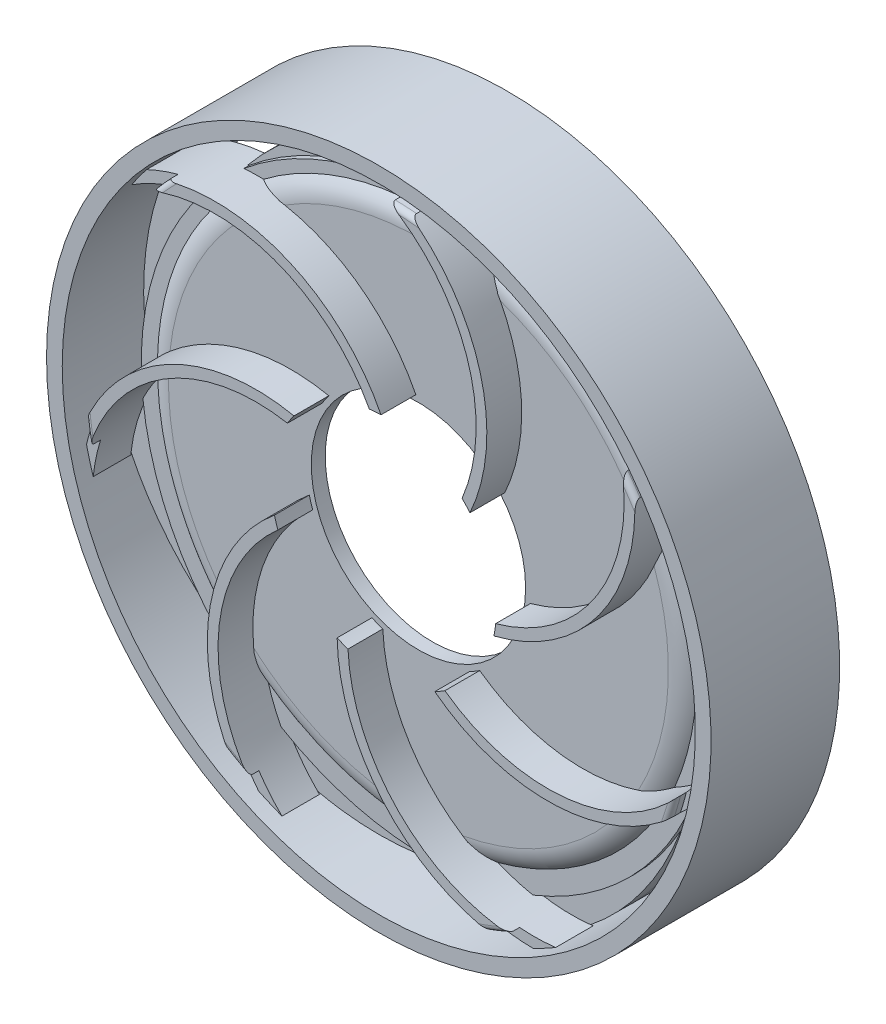
SolidWorks part; units mm, degrees
ref_plane "Ön Düzlem" through (0, 0, 0) normal (0, 0, 1) x (1, 0, 0)
ref_plane "Üst Düzlem" through (0, 0, 0) normal (0, 1, 0) x (1, 0, 0)
ref_plane "Sağ Düzlem" through (0, 0, 0) normal (1, 0, 0) x (0, 0, -1)
sketch "Sketch1" plane through (0, 0, 0) normal (0, 0, 1) x (1, 0, 0)
  circle A0 centre (0, 0) radius 51
extrude "Boss-Extrude1" add sketch "Sketch1" along normal blind 2.6
sketch "Sketch13" plane through (0, 0, 0) normal (0, 0, -1) x (-1, 0, 0)
  line L0 (0, 0) -> (0, 51) construction
  line L1 (0, 51) -> (0, 59.5)
  line L2 (0, 0) -> (39.8734, 31.798) construction
  line L3 (0, 0) -> (49.7213, -11.3486) construction
  line L4 (0, 0) -> (22.1281, -45.9494) construction
  line L5 (0, 0) -> (-22.1281, -45.9494) construction
  line L6 (0, 0) -> (-49.7213, -11.3486) construction
  line L7 (0, 0) -> (-39.8734, 31.798) construction
  line L8 (39.8734, 31.798) -> (46.519, 37.0976)
  line L9 (49.7213, -11.3486) -> (58.0082, -13.24)
  line L10 (22.1281, -45.9494) -> (25.8161, -53.6076)
  line L11 (-22.1281, -45.9494) -> (-25.8161, -53.6076)
  line L12 (-49.7213, -11.3486) -> (-58.0082, -13.24)
  line L13 (-39.8734, 31.798) -> (-46.519, 37.0976)
  circle A0 centre (0, 0) radius 51 construction
  circle A1 centre (0, 0) radius 51
  spline S0 degree 3 poles (39.8734, 31.798) (31.9324, 46.3417) (16.4942, 57.3969) (0, 59.5) knots 0 0 0 0 1 1 1 1
  spline S1 degree 3 poles (49.7213, -11.3486) (56.141, 3.9278) (55.1586, 22.8907) (46.519, 37.0976) knots 0 0 0 0 1 1 1 1
  spline S2 degree 3 poles (22.1281, -45.9494) (38.0742, -41.4438) (52.2875, -28.8526) (58.0082, -13.24) knots 0 0 0 0 1 1 1 1
  spline S3 degree 3 poles (-22.1281, -45.9494) (-8.6632, -55.6074) (10.0428, -58.8693) (25.8161, -53.6076) knots 0 0 0 0 1 1 1 1
  spline S4 degree 3 poles (-49.7213, -11.3486) (-48.8771, -27.8975) (-39.7643, -44.5562) (-25.8161, -53.6076) knots 0 0 0 0 1 1 1 1
  spline S5 degree 3 poles (-39.8734, 31.798) (-52.2855, 20.8198) (-59.6281, 3.3086) (-58.0082, -13.24) knots 0 0 0 0 1 1 1 1
  spline S6 degree 3 poles (0, 51) (-16.3219, 53.8594) (-34.5907, 48.682) (-46.519, 37.0976) knots 0 0 0 0 1 1 1 1
  circle M1 centre (0, 0) radius 51
extrude "Boss-Extrude12" add sketch "Sketch13" along normal blind 3.5 separate body contours S6 L13 M1 | S5 L12 M1 | S4 L11 M1 | S3 L10 M1 | S2 L9 M1 | S1 L8 M1 | S0 L1 M1 region at (-14.9152, 50.6485, 0) region at (30.2991, 43.24, 0) region at (-48.8981, 19.9176, 0) region at (52.6975, 3.2709, 0) region at (35.4137, -39.1612, 0) region at (-46.0596, -25.8116, 0) region at (-8.5374, -52.1042, 0)
sketch "Sketch17" plane through (0, 0, -3.5) normal (0, 0, -1) x (-1, 0, 0)
  circle A0 centre (0, 0) radius 51
  circle A1 centre (0, 0) radius 51.583
extrude "Boss-Extrude17" add sketch "Sketch17" against normal blind 3.55
sketch "Sketch18" plane through (0, 0, -3.5) normal (0, 0, -1) x (-1, 0, 0)
  line L0 (0, 59.5) -> (0, 57.9874)
  line L1 (0, 51.583) -> (0, 59.5) construction
  line L2 (38.1469, 34.7219) -> (37.6476, 34.4043)
  arc A0 (37.6476, 34.4043) -> (33.9454, 38.0618) centre (0, 0) ccw
  spline S0 degree 3 poles (-2791.739, 934.1905) (2717.5594, -1730.7665) (-2165.1588, 2407.9814) (1350.0187, -2586.5321) knots -6.738439 -6.738439 -6.738439 -6.738439 7.54991 7.54991 7.54991 7.54991 only from (38.1469, 34.7219) to (0, 59.5) construction
  spline S1 degree 3 poles (38.1469, 34.7219) (29.8227, 47.8074) (15.3698, 57.5402) (0, 59.5) knots 0.06817 0.06817 0.06817 0.06817 1 1 1 1
  spline S2 degree 1 poles (36.8813, 33.9168) (-0.1897, 58.012) knots 0 0 1 1 construction
  spline S3 degree 3 poles (36.8813, 33.9168) (35.867, 35.5112) (33.6642, 38.5799) (28.5725, 44.272) (21.107, 50.3681) (10.8625, 55.6485) (3.5383, 57.5367) (-0.1897, 58.012) knots 0.06817 0.06817 0.06817 0.06817 0.184649 0.301127 0.534085 0.767042 1 1 1 1 only from (33.9454, 38.0618) to (0, 57.9874)
  dimension "D1" = 1.5
extrude "Boss-Extrude18" add sketch "Sketch18" along normal blind 8
pattern_circular "CirPattern9" count 7 over 360 about axis through (0, 0, -3.5) along (0, 0, -1) of "Boss-Extrude18"
chamfer "Chamfer4" distance 8 distance2 6 7 edges at (49.1406, -14.6973, -11.5) (42.1295, 29.2561, -11.5) (3.394, 51.179, -11.5) (-37.8972, 34.5631, -11.5) (-50.6511, -8.0795, -11.5) (-25.2636, -44.6381, -11.5) (19.1479, -47.5833, -11.5) first distance on face at (49.0818, -14.6903, -6.7) first distance on face at (42.0874, 29.2145, -6.7) first distance on face at (3.4003, 51.1202, -6.7) first distance on face at (-37.8473, 34.5314, -6.7) first distance on face at (-50.5951, -8.0603, -6.7) first distance on face at (-25.2438, -44.5824, -6.7) first distance on face at (19.1167, -47.533, -6.7)
fillet "Fillet2" radius 5 1 edges at (51, 0, 2.6)
sketch "Sketch19" plane through (0, 0, -11.5) normal (0, 0, -1) x (-1, 0, 0)
  circle A0 centre (0, 0) radius 59.0701
  circle A1 centre (0, 0) radius 62
extrude "Boss-Extrude19" add sketch "Sketch19" along normal blind 2.5 and the other way blind 21.5
sketch "Sketch20" plane through (0, 0, 2.6) normal (0, 0, 1) x (1, 0, 0)
  line L0 (0, 0) -> (0, 51) construction
  circle A0 centre (0, 0) radius 51 construction
  circle A1 centre (0, 0) radius 20
extrude "Cut-Extrude2" cut sketch "Sketch20" against normal through all
sketch "Sketch21" plane through (0, 0, 2.6) normal (0, 0, 1) x (1, 0, 0)
  line L0 (0, 0) -> (0, 20) construction
  line L1 (0, 20) -> (-46.1002, 36.7637) construction
  line L2 (-40.3292, 32.1614) -> (-46.1829, 36.8296) construction
  line L3 (-23.0501, 28.3818) -> (-31.4228, 5.3569) construction
  circle A0 centre (0, 0) radius 20 construction
  arc A1 (0, 20) -> (-46.3162, 36.6618) centre (-31.4228, 5.3569) ccw
  arc A2 (0, 20) -> (-2.1628, 19.8827) centre (0, 0) ccw
  arc A3 (-2.1628, 19.8827) -> (-49.1142, 32.8188) centre (-31.4228, 5.3569) ccw
  circle A4 centre (0, 0) radius 59.0701 construction
  arc A5 (-46.3162, 36.6618) -> (-49.1142, 32.8188) centre (0, 0) ccw
  circle A7 centre (-31.4228, 5.3569) radius 34.6672 construction
  circle A8 centre (-31.4228, 5.3569) radius 32.6672 construction
  point P10 (1.2444, 5.3569)
  point P15 (1.7296, 15.4926)
  dimension "D1" = 2
extrude "Boss-Extrude20" add sketch "Sketch21" along normal blind 6.5
pattern_circular "CirPattern10" count 7 over 360 about axis through (0, 0, 2.6) along (0, 0, 1) of "Boss-Extrude20"
sketch "Sketch22" plane through (0, 0, -3.5) normal (0, 0, -1) x (-1, 0, 0)
  line L0 (40.3292, 32.1614) -> (45.3364, 36.1546) construction
  line L1 (46.1829, 36.8296) -> (45.3364, 36.1546) construction
  line L2 (39.8734, 31.798) -> (45.3364, 36.1546)
  line L3 (46.1002, 36.7637) -> (45.3364, 36.1546)
  arc A0 (46.3162, 36.6618) -> (24.9411, 39.4127) centre (31.4228, 5.3569) ccw construction
  arc A1 (46.1002, 36.7637) -> (31.6088, 40.0236) centre (31.4228, 5.3569) ccw
  circle A2 centre (0, 0) radius 51 construction
  arc A3 (39.8734, 31.798) -> (31.6088, 40.0236) centre (0, 0) ccw
extrude "Boss-Extrude21" add sketch "Sketch22" against normal blind 3.5
pattern_circular "CirPattern11" count 7 over 360 about axis through (0, 0, 0) along (0, 0, 1) of "Boss-Extrude21"
sketch "Sketch23" plane through (0, 0, 9.1) normal (0, 0, 1) x (1, 0, 0)
  line L0 (44.4062, 16.5772) -> (43.2978, 19.3933)
  arc A2 (19.4986, -4.4504) -> (46.049, 36.9969) centre (12.2148, 29.4429) ccw construction
  arc A3 (19.8655, -2.3157) -> (42.9249, 40.5799) centre (12.2148, 29.4429) ccw construction
  arc A4 (19.4986, -4.4504) -> (19.8655, -2.3157) centre (0, 0) ccw
  arc A5 (19.4986, -4.4504) -> (46.049, 36.9969) centre (12.2148, 29.4429) ccw
  arc A6 (46.049, 36.9969) -> (42.9249, 40.5799) centre (0, 0) ccw
  arc A7 (19.8655, -2.3157) -> (42.9249, 40.5799) centre (12.2148, 29.4429) ccw
  arc A9 (44.4062, 16.5772) -> (46.049, 36.9969) centre (12.2148, 29.4429) ccw
  arc A10 (46.049, 36.9969) -> (42.9249, 40.5799) centre (0, 0) ccw
  arc A11 (43.2978, 19.3933) -> (42.9249, 40.5799) centre (12.2148, 29.4429) ccw
  dimension "D1" = 0
extrude "Boss-Extrude22" add sketch "Sketch23" against normal blind 9.1
pattern_circular "CirPattern13" count 7 over 360 about axis through (0, 0, 10) along (0, 0, -1) of "Boss-Extrude22"
sketch "Sketch24" plane through (0, 0, 2.6) normal (0, 0, 1) x (1, 0, 0)
  circle A0 centre (0, 0) radius 21.0053
extrude "Cut-Extrude3" cut sketch "Sketch24" along normal blind 12.6
sketch "Sketch25" plane through (0, 0, 10) normal (0, 0, 1) x (1, 0, 0)
  circle A0 centre (0, 0) radius 59.0701 construction
  circle A1 centre (0, 0) radius 59.0701
  circle A2 centre (0, 0) radius 56.0701
  dimension "D1" = 3
extrude "Cut-Extrude4" cut sketch "Sketch25" against normal blind 3
fillet "Fillet3" radius 1 7 edges at (-55.2798, -9.3809, 9.1) (-27.1321, -49.0684, 9.1) (21.4466, -51.8064, 9.1) (53.8756, -15.5331, 9.1) (45.7352, 32.4369, 9.1) (3.1552, 55.9813, 9.1) (-41.8007, 37.3706, 9.1)
sketch "Sketch26" plane through (0, 0, 0) normal (0, 0, -1) x (-1, 0, 0)
  circle A0 centre (0, 0) radius 52
extrude "Cut-Extrude5" cut sketch "Sketch26" along normal blind 30
sketch "Sketch27" plane through (0, 0, 0) normal (0, 0, -1) x (-1, 0, 0)
  circle A0 centre (0, 0) radius 20 construction
  circle A1 centre (0, 0) radius 20
  circle A2 centre (0, -1.0126) radius 53.3209
extrude "Boss-Extrude23" add sketch "Sketch27" against normal blind 1
